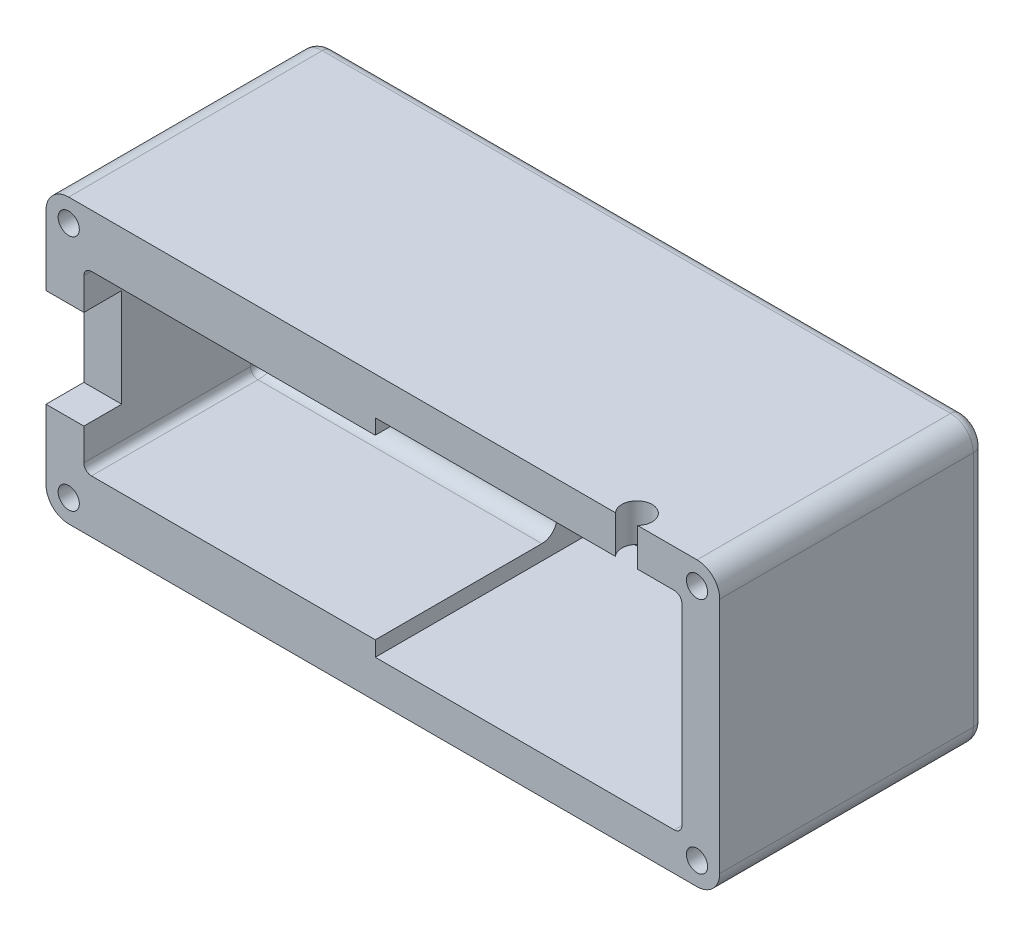
SolidWorks part; units mm, degrees
ref_plane "정면" through (0, 0, 0) normal (0, 0, 1) x (1, 0, 0)
ref_plane "윗면" through (0, 0, 0) normal (0, 1, 0) x (1, 0, 0)
ref_plane "우측면" through (0, 0, 0) normal (1, 0, 0) x (0, 0, -1)
sketch "스케치1" plane through (0, 0, 0) normal (0, 0, 1) x (1, 0, 0)
  line L0 (-44.5, 18.7) -> (44.5, 18.7)
  line L1 (-39.5, -13.7) -> (39.5, -13.7)
  line L2 (-39.5, -13.7) -> (-39.5, 13.7)
  line L3 (-39.5, 13.7) -> (39.5, 13.7)
  line L4 (39.5, -13.7) -> (39.5, 13.7)
  line L5 (-39.5, -13.7) -> (39.5, 13.7) construction
  line L6 (-39.5, 13.7) -> (39.5, -13.7) construction
  line L7 (44.5, -18.7) -> (44.5, 18.7)
  line L8 (-44.5, -18.7) -> (44.5, -18.7)
  line L9 (-44.5, -18.7) -> (-44.5, 18.7)
  point P0 (0, 0)
  dimension "D1" = 27.4
  dimension "D2" = 79
  dimension "D3" = 5
extrude "보스-돌출1" add sketch "스케치1" along normal blind 35
extrude "보스-돌출2" add sketch "스케치1<2>" along normal blind 5 contours L1 L4 L3 L2 region at (0, 0, 0)
sketch "스케치1<2>" plane through (0, 0, 0) normal (0, 0, 1) x (1, 0, 0) same geometry as "스케치1"
fillet "필렛1" radius 3 4 edges at (44.5, -18.7, 17.5) (44.5, 18.7, 17.5) (-44.5, -18.7, 17.5) (-44.5, 18.7, 17.5)
sketch "스케치2" plane through (0, 0, 5) normal (0, 0, 1) x (1, 0, 0)
  line L0 (7.25, 0) -> (0, 0) construction
  line L1 (3, 4.25) -> (11.5, 4.25)
  line L2 (3, 4.25) -> (3, -4.25)
  line L3 (3, -4.25) -> (11.5, -4.25)
  line L4 (11.5, 4.25) -> (11.5, -4.25)
  line L5 (3, 4.25) -> (11.5, -4.25) construction
  line L6 (3, -4.25) -> (11.5, 4.25) construction
  line L8 (39.5, -13.7) -> (39.5, 13.7) construction
  point P0 (7.25, 0)
  dimension "D1" = 8.5
  dimension "D2" = 8.5
  dimension "D3" = 36.5
extrude "컷-돌출1" cut sketch "스케치2" against normal blind 2.5
sketch "스케치4" plane through (0, 0, 0) normal (0, 0, 1) x (1, 0, 0)
  line L0 (3, 4.25) -> (11.5, -4.25) construction
  circle A0 centre (7.25, 0) radius 4
  dimension "D1" = 8
extrude "컷-돌출3" cut sketch "스케치4" against normal blind 2.5 and the other way through all
fillet "필렛3" radius 1.5 8 edges at (43.6213, 17.8213, 0) (44.5, 0, 0) (43.6213, -17.8213, 0) (0, -18.7, 0) (-43.6213, -17.8213, 0) (-44.5, 0, 0) (-43.6213, 17.8213, 0) (0, 18.7, 0)
sketch "스케치6" plane through (0, 0, 5) normal (0, 0, 1) x (1, 0, 0)
  line L0 (-39.5, -13.7) -> (39.5, -13.7) construction
  line L1 (27.5, -10.2) -> (31, -10.2)
  line L2 (27.5, -10.2) -> (27.5, -13.7)
  line L3 (27.5, -13.7) -> (31, -13.7)
  line L4 (31, -10.2) -> (31, -13.7)
  line L5 (39.5, -13.7) -> (39.5, 13.7) construction
  dimension "D1" = 12
  dimension "D2" = 3.5
  dimension "D3" = 3.5
extrude "컷-돌출4" cut sketch "스케치6" against normal through all
sketch "스케치8" plane through (0, 0, 5) normal (0, 0, 1) x (1, 0, 0)
  line L1 (39.5, 13.7) -> (31.5, 13.7)
  line L2 (39.5, 13.7) -> (39.5, -13.7)
  line L3 (39.5, -13.7) -> (31.5, -13.7)
  line L4 (31.5, 13.7) -> (31.5, -13.7)
  dimension "D1" = 8
extrude "보스-돌출3" add sketch "스케치8" along normal blind 2.3
sketch "스케치9" plane through (0, 0, 5) normal (0, 0, 1) x (1, 0, 0)
  line L0 (-39.5, -13.7) -> (39.5, -13.7) construction
  line L1 (-39.5, 13.7) -> (-1, 13.7)
  line L2 (-39.5, 13.7) -> (-39.5, -13.7)
  line L3 (-39.5, -13.7) -> (-1, -13.7)
  line L4 (-1, 13.7) -> (-1, 5.2781)
  line L5 (39.5, -13.7) -> (39.5, 13.7) construction
  line L6 (-1, 5.2781) -> (-4.5123, 5.2781)
  line L7 (-4.5123, 5.2781) -> (-4.5123, -7.0443)
  line L8 (-4.5123, -7.0443) -> (-1, -7.0443)
  line L9 (-1, -7.0443) -> (-1, -13.7)
  dimension "D1" = 40.5
extrude "보스-돌출4" add sketch "스케치9" along normal blind 6
sketch "스케치11" plane through (0, 18.7, 0) normal (0, 1, 0) x (1, 0, 0)
  circle A0 centre (32.1934, -33.6289) radius 2
  dimension "D1" = 4
extrude "컷-돌출6" cut sketch "스케치11" against normal blind 6
sketch "스케치12" plane through (0, 0, 35) normal (0, 0, 1) x (1, 0, 0)
  line L0 (-44.5, 15.7) -> (-44.5, -15.7) construction
  line L1 (-44.5, 6.5) -> (-39.5, 6.5)
  line L2 (-44.5, 6.5) -> (-44.5, -6.5)
  line L3 (-44.5, -6.5) -> (-39.5, -6.5)
  line L4 (-39.5, 6.5) -> (-39.5, -6.5)
  line L5 (-39.5, 13.7) -> (-39.5, -13.7) construction
  line L6 (-39.5, 0) -> (0, 0) construction
  dimension "D1" = 13
extrude "컷-돌출7" cut sketch "스케치12" against normal blind 5
fillet "필렛4" radius 1 2 edges at (39.5, -13.7, 21.15) (39.5, 13.7, 21.15)
sketch "스케치13" plane through (0, 0, 35) normal (0, 0, 1) x (1, 0, 0)
  line L0 (0, 0) -> (-44.5, 0) construction
  line L1 (-44.5, 6.5) -> (-44.5, -6.5) construction
  line L2 (0, 0) -> (0, 18.7) construction
  line L3 (30.7373, 18.7) -> (-41.5, 18.7) construction
  circle A0 centre (-41.5, 15.7) radius 1.4
  circle A1 centre (41.5, 15.7) radius 1.4
  circle A2 centre (41.5, -15.7) radius 1.4
  circle A3 centre (-41.5, -15.7) radius 1.4
  dimension "D1" = 2.8
extrude "컷-돌출8" cut sketch "스케치13" against normal blind 20
sketch "스케치14" plane through (0, 0, 35) normal (0, 0, 1) x (1, 0, 0)
  line L0 (-1, 5.2781) -> (-1, 13.7) construction
  line L1 (-39.5, 13.7) -> (-1, 13.7)
  line L2 (-39.5, 13.7) -> (-39.5, 11.7)
  line L3 (-39.5, 11.7) -> (-1, 11.7)
  line L4 (-1, 13.7) -> (-1, 11.7)
  line L5 (0, 0) -> (-44.5, 0) construction
  line L6 (-44.5, 6.5) -> (-44.5, -6.5) construction
  line L7 (-1, -13.7) -> (-1, -11.7)
  line L8 (-39.5, -11.7) -> (-1, -11.7)
  line L9 (-39.5, -13.7) -> (-39.5, -11.7)
  line L10 (-39.5, -13.7) -> (-1, -13.7)
  dimension "D1" = 2
extrude "보스-돌출5" add sketch "스케치14" against normal up to next
fillet "필렛5" radius 2 3 edges at (-39.5, 0, 11) (-20.25, -11.7, 11) (-20.25, 11.7, 11)
fillet "필렛6" radius 1 4 edges at (-38.9142, -11.1142, 11.5858) (-38.9142, 11.1142, 11.5858) (-39.5, -11.7, 24) (-39.5, 11.7, 24)
